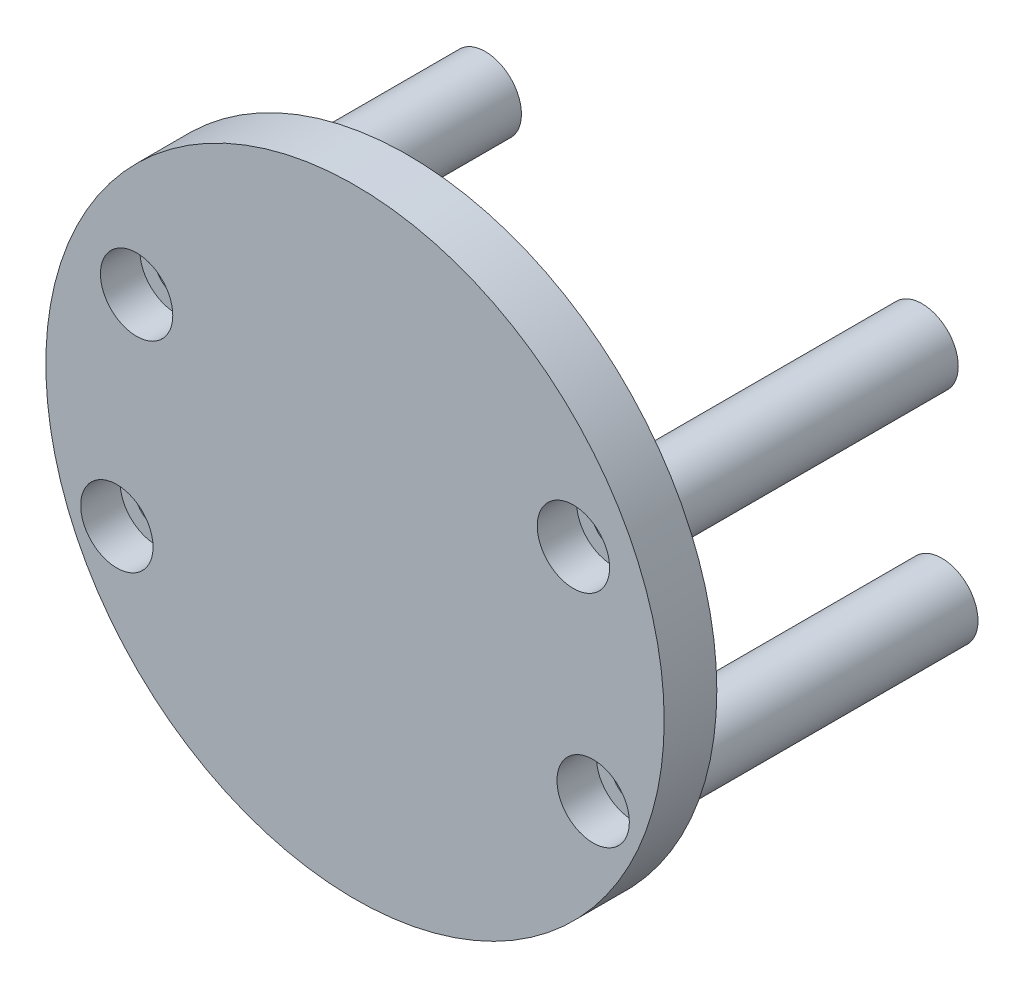
SolidWorks part; units mm, degrees
ref_plane "正面" through (0, 0, 0) normal (0, 0, 1) x (1, 0, 0)
ref_plane "平面" through (0, 0, 0) normal (0, 1, 0) x (1, 0, 0)
ref_plane "右側面" through (0, 0, 0) normal (1, 0, 0) x (0, 0, -1)
sketch "ｽｹｯﾁ1" plane through (0, 0, 0) normal (0, 0, 1) x (1, 0, 0)
  line L0 (-16.6, 0) -> (16.6, 0)
  line L1 (-16.6, 0) -> (-16.6, 8)
  line L2 (-16.6, 0) -> (-18.1, 0)
  line L3 (-18.1, 0) -> (-18.1, -8)
  line L4 (16.6, 0) -> (16.6, 8)
  line L5 (16.6, 0) -> (18.1, 0)
  line L6 (18.1, 0) -> (18.1, -8)
  circle A0 centre (-16.6, 8) radius 1.6
  circle A1 centre (-18.1, -8) radius 1.6
  circle A2 centre (16.6, 8) radius 2.75
  circle A3 centre (18.1, -8) radius 1.6
  circle A4 centre (0, 0) radius 23.5
  circle A5 centre (-16.6, 8) radius 2.75
  circle A6 centre (-18.1, -8) radius 2.75
  circle A7 centre (16.6, 8) radius 1.6
  circle A8 centre (18.1, -8) radius 2.75
  point P4 (0, 0)
  dimension "D2" = 3.2
  dimension "D5" = 3.2
  dimension "D7" = 5.5
  dimension "D9" = 3.2
  dimension "D10" = 47
  dimension "D11" = 5.5
  dimension "D12" = 5.5
  dimension "D13" = 3.2
  dimension "D14" = 5.5
  dimension "D1" = 8
  dimension "D3" = 1.5
  dimension "D4" = 8
  dimension "D6" = 8
  dimension "D8" = 1.5
extrude "ﾎﾞｽ - 押し出し1" add sketch "ｽｹｯﾁ1" along normal blind 3 and the other way blind 1 contours A4 A8 A6 A5 A2 region at (-22.8353, 0, 0)
extrude "ﾎﾞｽ - 押し出し2" add sketch "ｽｹｯﾁ1<4>" against normal blind 23.5 separate body contours A6 A1 | A8 A3 | A7 A2 | A5 A0 region at (14.7105, 9.8895, 0) region at (19.9895, -6.1105, 0) region at (-18.4895, 9.8895, 0) region at (-16.2105, -6.1105, 0)
sketch "ｽｹｯﾁ1<4>" plane through (0, 0, 0) normal (0, 0, 1) x (1, 0, 0) same geometry as "ｽｹｯﾁ1"
